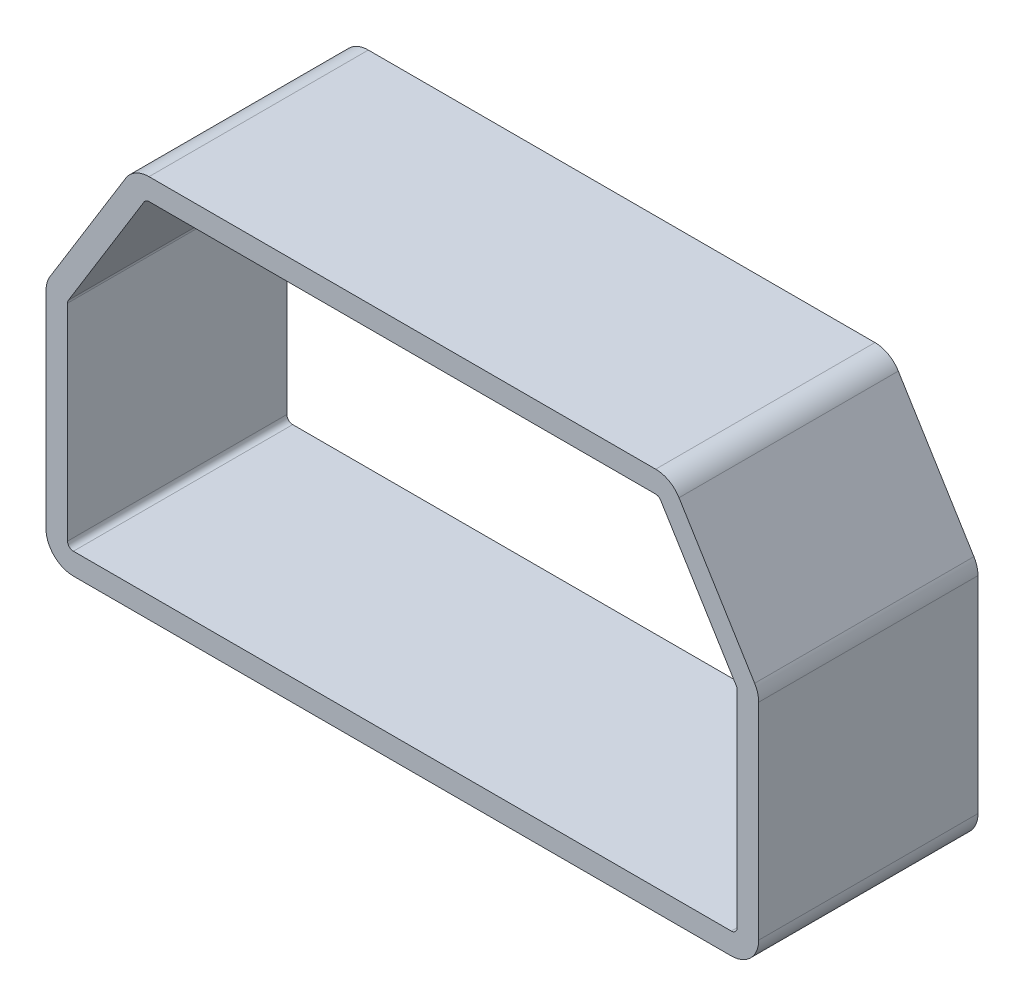
SolidWorks part; units mm, degrees
material "Custom Plastic"
ref_plane "X-Y Datum" through (0, 0, 0) normal (0, 0, 1) x (1, 0, 0)
ref_plane "X-Z Datum" through (0, 0, 0) normal (0, 1, 0) x (1, 0, 0)
ref_plane "Y-Z Datum" through (0, 0, 0) normal (1, 0, 0) x (0, 0, -1)
sketch "Sketch1" plane through (0, 0, 0) normal (0, 0, 1) x (1, 0, 0)
  line L0 (-82.55, -44.45) -> (-75.1791, 44.45)
  line L1 (-82.55, 44.45) -> (82.55, 44.45)
  line L2 (-82.55, 44.45) -> (-82.55, -44.45)
  line L3 (-82.55, -44.45) -> (82.55, -44.45)
  line L4 (82.55, 44.45) -> (82.55, -44.45)
  line L5 (-82.55, 44.45) -> (82.55, -44.45) construction
  line L6 (-82.55, -44.45) -> (82.55, 44.45) construction
  line L8 (0, 90.3576) -> (0, -90.3576) construction
  line L9 (82.55, -44.45) -> (75.1791, 44.45)
  point P0 (0, 0)
  point P12 (0, 0)
  point P13 (0, 0)
  dimension "D1" = 165.1
  dimension "D2" = 88.9
extrude "Boss-Extrude1" add sketch "Sketch1" along normal blind 50.8 contours L3 L9 L1 L0 | L1 L2 L0 | L9 L4 L1 region at (-80.093, 14.8167, 0) region at (0, -0.6924, 0) region at (80.093, 14.8167, 0)
sketch "Sketch2" plane through (0, 0, 0) normal (0, 0, -1) x (-1, 0, 0)
  line L0 (-82.55, 11.43) -> (-62.23, 44.45)
  line L1 (-82.55, 44.45) -> (-82.55, -44.45) construction
  line L2 (82.55, 44.45) -> (-82.55, 44.45) construction
  line L3 (0, -14.0019) -> (0, 14.0019) construction
  line L4 (82.55, 11.43) -> (62.23, 44.45)
  point P11 (0, 0)
  line M3 (-82.55, 44.45) -> (-82.55, -44.45)
  line M5 (82.55, -44.45) -> (82.55, 44.45)
  line M6 (82.55, 44.45) -> (-82.55, 44.45)
  dimension "D1" = 55.88
  dimension "D2" = 20.32
extrude "Cut-Extrude1" cut sketch "Sketch2" against normal through all contours L0 M3 M6 | L4 M5 M6 region at (75.7767, 33.4433, 0) region at (-75.7767, 33.4433, 0)
fillet "Fillet1" radius 6.35 6 edges at (82.55, -44.45, 25.4) (82.55, 11.43, 25.4) (62.23, 44.45, 25.4) (-62.23, 44.45, 25.4) (-82.55, 11.43, 25.4) (-82.55, -44.45, 25.4)
shell "Shell1" thickness 5 removed face at (0, 4.2293, 0)
sketch "Sketch4" plane through (0, 0, 45.8) normal (0, 0, -1) x (-1, 0, 0)
  line L6 (-59.8314, 38.8075) -> (-77.3497, 10.3402)
  line L7 (-77.55, 9.6327) -> (-77.55, -38.1)
  line L8 (-76.2, -39.45) -> (76.2, -39.45)
  line L9 (77.55, -38.1) -> (77.55, 9.6327)
  line L10 (77.3497, 10.3402) -> (59.8314, 38.8075)
  line L11 (58.6817, 39.45) -> (-58.6817, 39.45)
  line L12 (-59.8314, 38.8075) -> (-77.3497, 10.3402)
  line L13 (-77.55, 9.6327) -> (-77.55, -38.1)
  line L14 (-76.2, -39.45) -> (76.2, -39.45)
  line L15 (77.55, -38.1) -> (77.55, 9.6327)
  line L16 (77.3497, 10.3402) -> (59.8314, 38.8075)
  line L17 (58.6817, 39.45) -> (-58.6817, 39.45)
  arc A6 (76.2, -39.45) -> (77.55, -38.1) centre (76.2, -38.1) ccw
  arc A7 (76.2, -39.45) -> (77.55, -38.1) centre (76.2, -38.1) ccw
  arc A8 (77.55, 9.6327) -> (77.3497, 10.3402) centre (76.2, 9.6327) ccw
  arc A9 (77.55, 9.6327) -> (77.3497, 10.3402) centre (76.2, 9.6327) ccw
  arc A10 (59.8314, 38.8075) -> (58.6817, 39.45) centre (58.6817, 38.1) ccw
  arc A11 (59.8314, 38.8075) -> (58.6817, 39.45) centre (58.6817, 38.1) ccw
  arc A12 (-58.6817, 39.45) -> (-59.8314, 38.8075) centre (-58.6817, 38.1) ccw
  arc A13 (-58.6817, 39.45) -> (-59.8314, 38.8075) centre (-58.6817, 38.1) ccw
  arc A14 (-77.3497, 10.3402) -> (-77.55, 9.6327) centre (-76.2, 9.6327) ccw
  arc A15 (-77.3497, 10.3402) -> (-77.55, 9.6327) centre (-76.2, 9.6327) ccw
  arc A16 (-77.55, -38.1) -> (-76.2, -39.45) centre (-76.2, -38.1) ccw
  arc A17 (-77.55, -38.1) -> (-76.2, -39.45) centre (-76.2, -38.1) ccw
  dimension "D1" = 0
extrude "Cut-Extrude2" cut sketch "Sketch4" against normal through all
